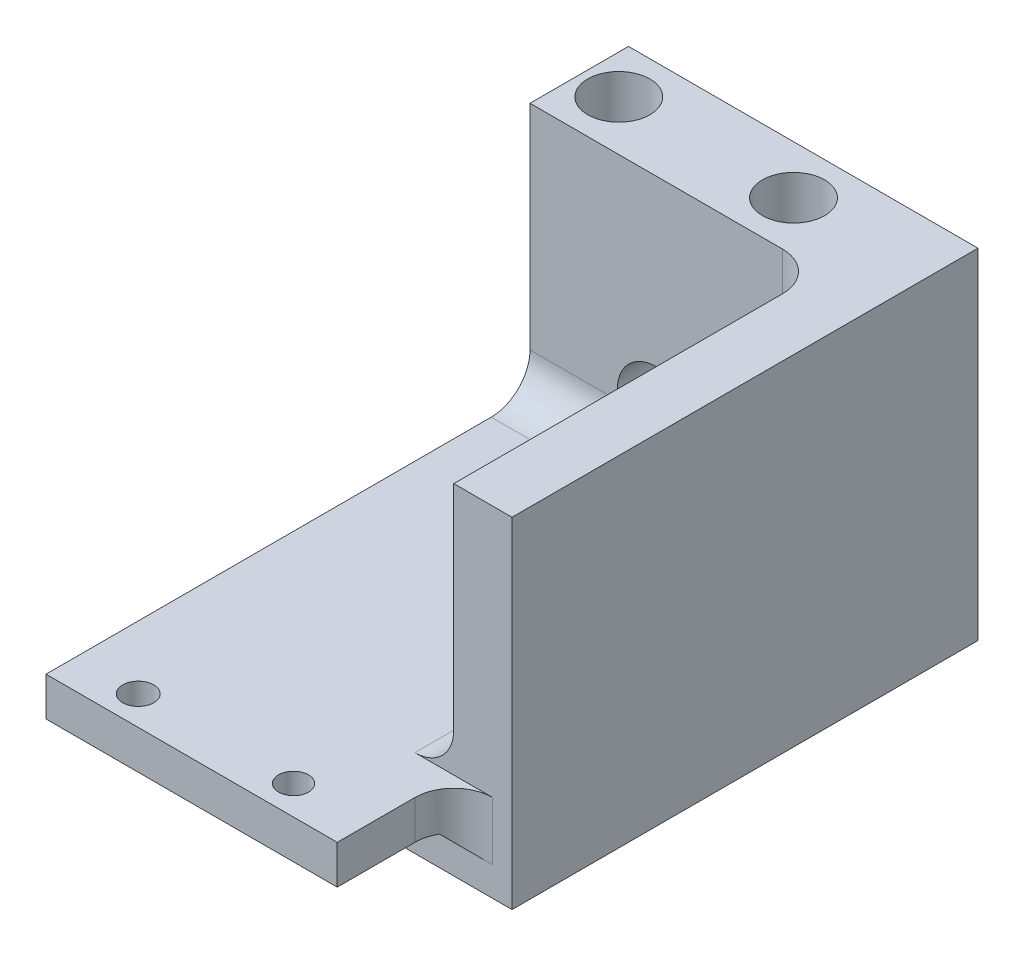
SolidWorks part; units mm, degrees
ref_plane "Front Plane" through (0, 0, 0) normal (0, 0, 1) x (1, 0, 0)
ref_plane "Top Plane" through (0, 0, 0) normal (0, 1, 0) x (1, 0, 0)
ref_plane "Right Plane" through (0, 0, 0) normal (1, 0, 0) x (0, 0, -1)
sketch "Sketch2" plane through (0, 0, 0) normal (0, 1, 0) x (1, 0, 0)
  line L1 (0, 0) -> (30, 0)
  line L2 (0, 0) -> (0, 60)
  line L3 (0, 60) -> (30, 60)
  line L4 (30, 0) -> (30, 60)
  circle A0 centre (6.5, 3) radius 1.6
  circle A1 centre (22.5, 3) radius 1.5445
  circle A2 centre (4, 55) radius 1.6
  circle A3 centre (22, 55) radius 1.6
  dimension "D3" = 3.2
  dimension "D8" = 3.2
  dimension "D9" = 3.2
  dimension "D1" = 30
  dimension "D2" = 3
  dimension "D4" = 16
  dimension "D5" = 7.5
  dimension "D6" = 60
  dimension "D7" = 4
  dimension "D10" = 5
  dimension "D11" = 5
  dimension "D12" = 8
extrude "Boss-Extrude1" add sketch "Sketch2" along normal blind 35
sketch "Sketch3" plane through (0, 35, 0) normal (0, 1, 0) x (1, 0, 0)
  line L0 (30, 0) -> (30, 60) construction
  line L1 (0, 0) -> (30, 0)
  line L2 (0, 0) -> (0, 49.856)
  line L3 (0, 49.856) -> (30, 49.856)
  line L4 (30, 0) -> (30, 49.856)
extrude "Cut-Extrude1" cut sketch "Sketch3" against normal blind 26
sketch "Sketch4" plane through (0, 0, 0) normal (0, -1, 0) x (1, 0, 0)
  line L0 (30, 0) -> (30, -60) construction
  line L1 (0, 0) -> (30, 0)
  line L2 (0, 0) -> (0, -12)
  line L3 (0, -12) -> (30, -12)
  line L4 (30, 0) -> (30, -12)
  dimension "D1" = 12
extrude "Cut-Extrude2" cut sketch "Sketch4" against normal blind 5
sketch "Sketch5" plane through (0, 35, 0) normal (0, 1, 0) x (1, 0, 0)
  circle A0 centre (4, 55) radius 3.2
  circle A1 centre (22, 55) radius 3.2
  dimension "D1" = 6.4
  dimension "D2" = 6.4
extrude "Cut-Extrude3" cut sketch "Sketch5" against normal blind 26
sketch "Sketch6" plane through (0, 0, -60) normal (0, 0, -1) x (-1, 0, 0)
  line L0 (-30, 0) -> (0, 0) construction
  circle A0 centre (-13, 14) radius 4
  dimension "D2" = 8
  dimension "D1" = 14
extrude "Cut-Extrude4" cut sketch "Sketch6" against normal blind 26
sketch "Sketch7" plane through (30, 0, 0) normal (1, 0, 0) x (0, 0, -1)
  line L0 (12, 0) -> (60, 0) construction
  line L1 (60, 35) -> (49.856, 35)
  line L2 (60, 35) -> (60, 0)
  line L3 (60, 0) -> (49.856, 0)
  line L4 (49.856, 35) -> (49.856, 0)
sketch "Sketch8" plane through (30, 0, 0) normal (1, 0, 0) x (0, 0, -1)
  line L1 (12, 0) -> (60, 0)
  line L2 (12, 0) -> (12, 35)
  line L3 (12, 35) -> (60, 35)
  line L4 (60, 0) -> (60, 35)
extrude "Boss-Extrude3" add sketch "Sketch8" along normal blind 6
chamfer "Chamfer1" distance 2 angle 45 1 edges at (15, 5, -12)
fillet "Fillet1" radius 4 1 edges at (30, 6, -12)
fillet "Fillet2" radius 4 3 edges at (15, 9, -49.856) (30, 22, -49.856) (30, 9, -30.928)
